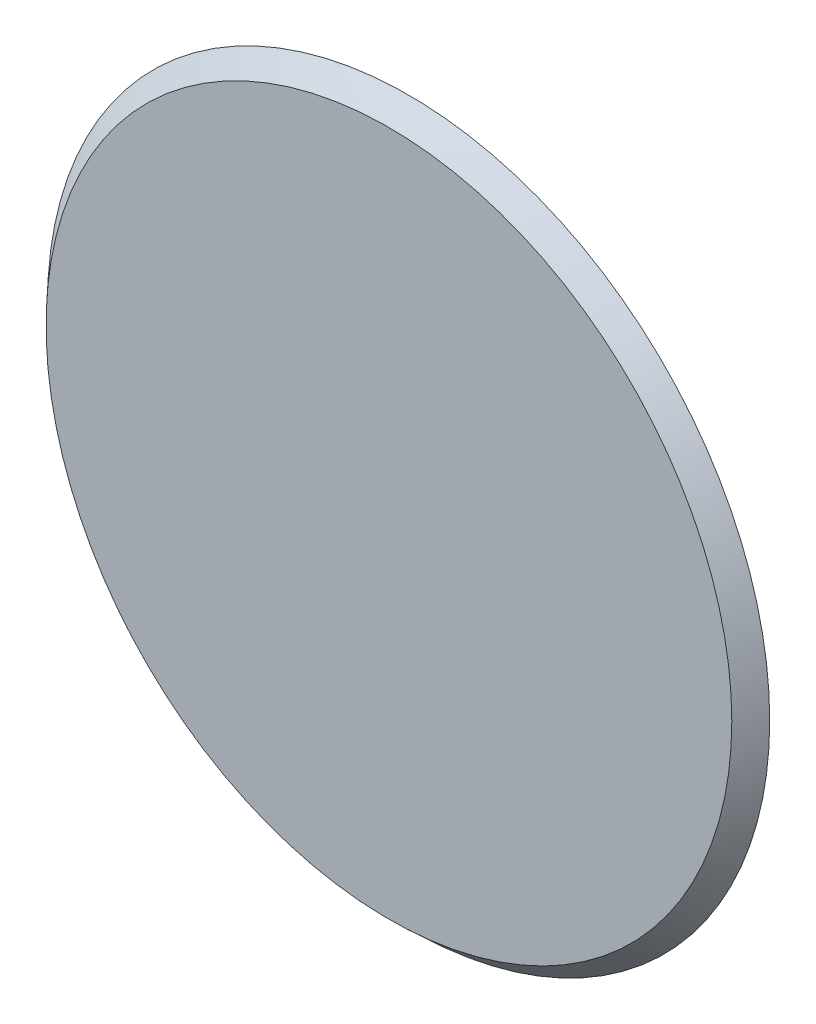
SolidWorks part; units mm, degrees
material "Stainless Steel 2205"
ref_plane "Front Plane" through (0, 0, 0) normal (0, 0, 1) x (1, 0, 0)
ref_plane "Top Plane" through (0, 0, 0) normal (0, 1, 0) x (1, 0, 0)
ref_plane "Right Plane" through (0, 0, 0) normal (1, 0, 0) x (0, 0, -1)
sketch "Sketch1" plane through (0, 0, 0) normal (0, 0, 1) x (1, 0, 0)
  circle A0 centre (0, 0) radius 1000
  dimension "D1" = 2000
extrude "Boss-Extrude2" add sketch "Sketch1" along normal blind 1
dome "Dome1" faces to dome 1 distance 1000 reverse direction no elliptical dome no face at (1000, 0, 1) parameters "D1"=1000
ref_plane "Plane1" through (0, 0, 1001) normal (0, 0, 1) x (1, 0, 0)
sketch "Sketch2" plane through (0, 0, 1001) normal (0, 0, 1) x (1, 0, 0)
  circle A0 centre (0, 0) radius 1000
  dimension "D1" = 2000
extrude "Cut-Extrude1" cut sketch "Sketch2" against normal blind 300
sketch "Sketch4" plane through (0, 0, 0) normal (0, 0, -1) x (-1, 0, 0)
  circle A0 centre (0, 0) radius 1000
extrude "Cut-Extrude2" cut sketch "Sketch4" against normal blind 660
